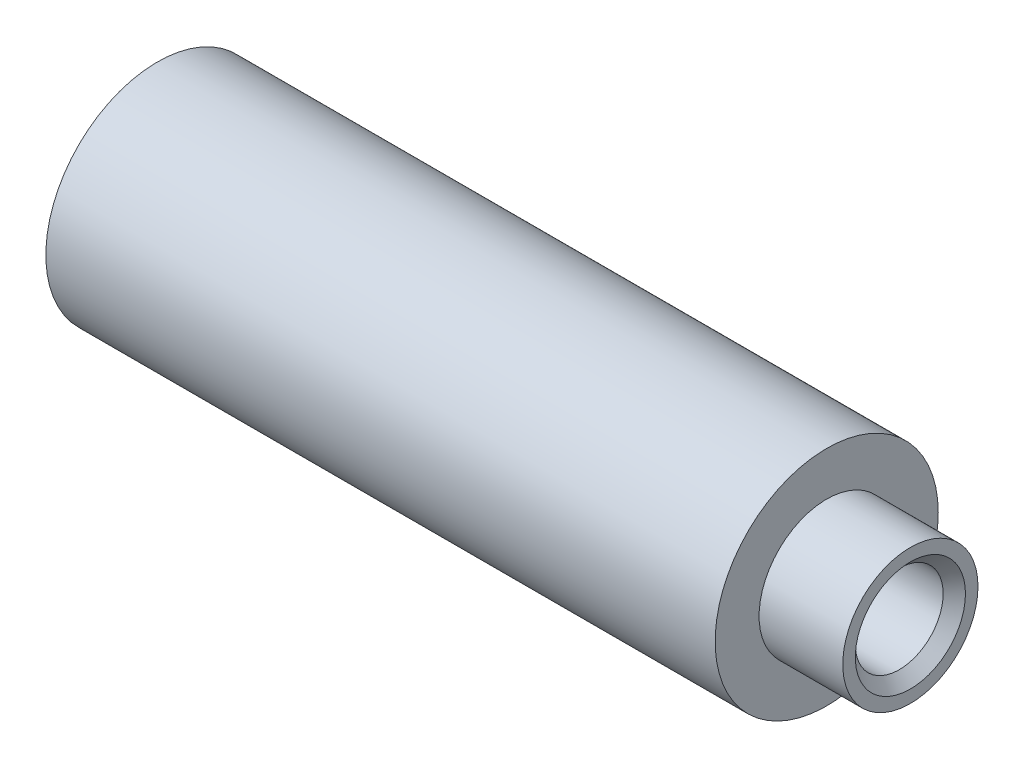
SolidWorks part; units mm, degrees
ref_plane "Ebene vorne" through (0, 0, 0) normal (0, 0, 1) x (1, 0, 0)
ref_plane "Ebene oben" through (0, 0, 0) normal (0, 1, 0) x (1, 0, 0)
ref_plane "Ebene rechts" through (0, 0, 0) normal (1, 0, 0) x (0, 0, -1)
sketch "Skizze1" plane through (0, 0, 0) normal (1, 0, 0) x (0, 0, -1)
  circle A0 centre (0, 0) radius 1.575
  circle A1 centre (0, 0) radius 4
  dimension "D1" = 8
  dimension "D2" = 3.15
extrude "Aufsatz-Linear austragen1" add sketch "Skizze1" along normal blind 27
sketch "Skizze2" plane through (27, 0, 0) normal (1, 0, 0) x (0, 0, -1)
  circle A0 centre (0, 0) radius 2.425
  dimension "D1" = 4.85
extrude "Schnitt-Linear austragen1" cut sketch "Skizze2" against normal blind 3 flip side to cut
chamfer "Fase1" distance 0.4 angle 45 2 edges at (0, 0, -1.575) (27, 0, -1.575)
